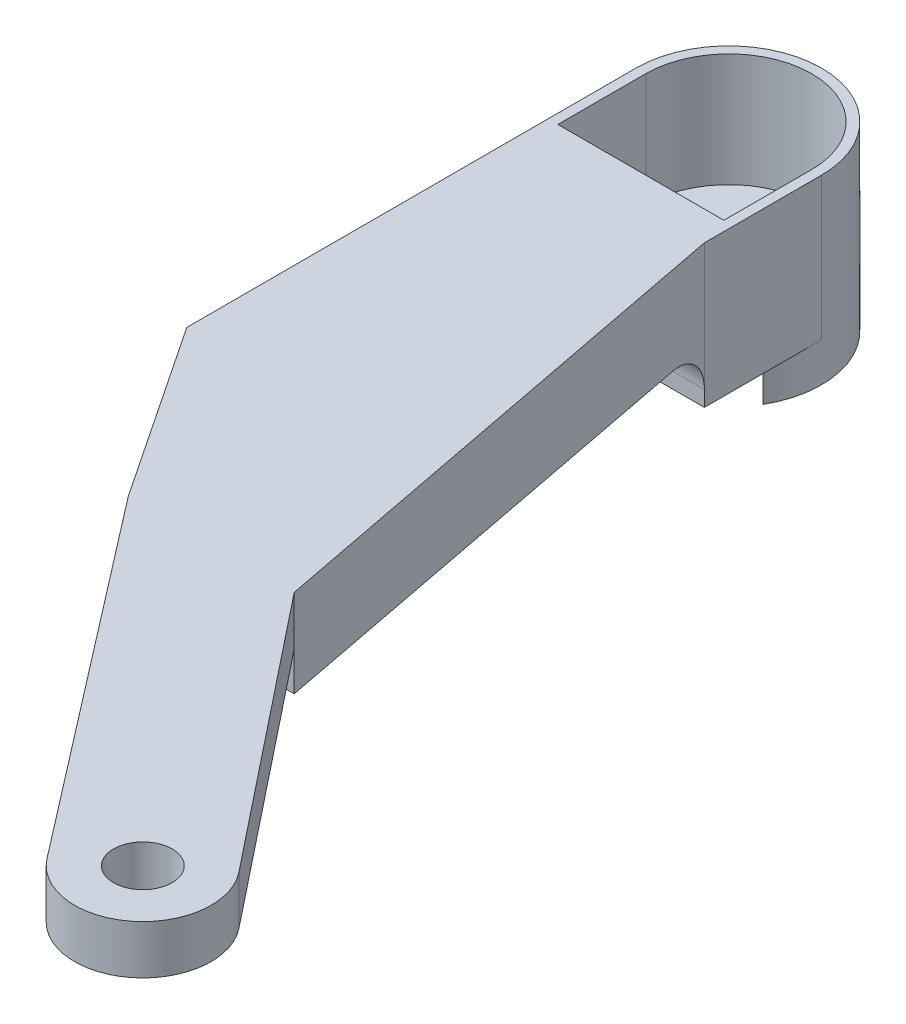
SolidWorks part; units mm, degrees
ref_plane "Front Plane" through (0, 0, 0) normal (0, 0, 1) x (1, 0, 0)
ref_plane "Top Plane" through (0, 0, 0) normal (0, 1, 0) x (1, 0, 0)
ref_plane "Right Plane" through (0, 0, 0) normal (1, 0, 0) x (0, 0, -1)
sketch "Sketch1" plane through (0, 0, 0) normal (0, 1, 0) x (1, 0, 0)
  line L0 (-2.75, 0) -> (-5.5779, -4.898)
  line L1 (2.75, 0) -> (5.5779, -4.898)
  line L2 (5.5779, -4.898) -> (-5.5779, -4.898) construction
  line L4 (0, -4.898) -> (0, 0) construction
  circle A0 centre (0, 0) radius 2.75
  circle A1 centre (0, 0) radius 4.75
  dimension "D1" = 5.5
  dimension "D2" = 2
  dimension "D3" = 60
extrude "Boss-Extrude1" add sketch "Sketch1" along normal blind 2 contours L1 A1 L0 A0 region at (-3.5365, 0, 1.1249)
sketch "Sketch2" plane through (0, 2, 0) normal (0, 1, 0) x (1, 0, 0)
  arc A0 (4.1174, -2.3684) -> (-4.1174, -2.3684) centre (0, 0) ccw construction
  circle A1 centre (0, 0) radius 4.75
  circle A2 centre (0, 0) radius 1.4
  dimension "D1" = 2.8
extrude "Boss-Extrude2" add sketch "Sketch2" along normal blind 1.5
sketch "Sketch3" plane through (0, 3.5, 0) normal (0, 1, 0) x (1, 0, 0)
  line L0 (-4.75, 0) -> (-4.75, -6)
  line L1 (-4.75, -6) -> (4.75, -6)
  line L2 (4.75, -6) -> (4.75, 0)
  line L3 (-4.75, 0) -> (4.75, 0) construction
  circle A0 centre (0, 0) radius 4.5
  circle A1 centre (0, 0) radius 4.75 construction
  circle A2 centre (0, 0) radius 4.75
  point P10 (-4.748, -0.1383)
  point P11 (-4.75, -0.1031)
  circle M5 centre (0, 0) radius 4.75
  dimension "D1" = 9
  dimension "D2" = 1.5
extrude "Boss-Extrude3" add sketch "Sketch3" against normal blind 1.5 contours L1 L2 L0 M5 region at (0, 3.5, 4.8624)
sketch "Sketch4" plane through (0, 3.5, 0) normal (0, 1, 0) x (1, 0, 0)
  line L0 (4.75, -6) -> (4.75, 0) construction
  line L1 (-4.75, -6) -> (4.75, -6)
  line L2 (-4.75, -6) -> (-4.75, -4.5)
  line L3 (-4.75, -4.5) -> (4.75, -4.5)
  line L4 (4.75, -6) -> (4.75, -4.5)
  dimension "D1" = 1.5
extrude "Boss-Extrude4" add sketch "Sketch4" along normal offset from surface (2.3 mm away) 3.8 up to face at (0, 2, 1.7587)
sketch "Sketch5" plane through (0, 5.8, 0) normal (0, 1, 0) x (1, 0, 0)
  line L0 (-4.75, -4.5) -> (-4.75, -23)
  line L1 (-4.75, -23) -> (1.25, -32)
  line L2 (1.25, -32) -> (9.75, -32)
  line L3 (9.75, -32) -> (4.75, -6)
  line L4 (4.75, -6) -> (4.75, -4.5)
  line L5 (4.75, -4.5) -> (-4.75, -4.5)
  dimension "D1" = 32
  dimension "D2" = 9
  dimension "D3" = 6
  dimension "D4" = 5
extrude "Boss-Extrude5" add sketch "Sketch5" along normal blind 1
sketch "Sketch6" plane through (0, 6.8, 0) normal (0, 1, 0) x (1, 0, 0)
  line L0 (9.75, -32) -> (20.7396, -45.8218)
  line L1 (1.25, -32) -> (15.2278, -50.1365)
  line L2 (1.25, -32) -> (9.75, -32) construction
  line L3 (1.25, -32) -> (9.75, -32)
  line L10 (4.75, -4.5) -> (-4.75, -4.5)
  line L11 (-4.75, -4.5) -> (-4.75, -23)
  line L12 (-4.75, -23) -> (1.25, -32)
  line L13 (1.25, -32) -> (9.75, -32)
  line L14 (9.75, -32) -> (4.75, -6)
  line L15 (4.75, -6) -> (4.75, -4.5)
  line L16 (4.75, -4.5) -> (-4.75, -4.5)
  line L17 (-4.75, -4.5) -> (-4.75, -23)
  line L18 (-4.75, -23) -> (1.25, -32)
  line L19 (1.25, -32) -> (9.75, -32)
  line L20 (9.75, -32) -> (4.75, -6)
  line L21 (4.75, -6) -> (4.75, -4.5)
  circle A0 centre (18, -48) radius 1.5
  circle A1 centre (18, -48) radius 3.5
  line M9 (4.75, -4.5) -> (-4.75, -4.5)
  line M10 (-4.75, -4.5) -> (-4.75, -23)
  line M11 (-4.75, -23) -> (1.25, -32)
  line M12 (1.25, -32) -> (9.75, -32)
  line M13 (9.75, -32) -> (4.75, -6)
  line M14 (4.75, -6) -> (4.75, -4.5)
  dimension "D3" = 3
  dimension "D1" = 18
  dimension "D2" = 48
  dimension "D4" = 2
  dimension "D5" = 0
extrude "Boss-Extrude6" add sketch "Sketch6" along normal blind 1.5 contours M14 M9 M10 M11 M12 M13 | A1 L0 L1 M12 | A1 A0 region at (10.768, 6.8, 39.0264) region at (1.6419, 6.8, 18.3842) region at (21.211, 6.8, 46.8791)
sketch "Sketch7" plane through (0, 3.5, 0) normal (0, 1, 0) x (1, 0, 0)
  line L0 (-4.75, 0) -> (-4.75, -4.5)
  line L1 (-4.75, -4.5) -> (-4.25, -4.5)
  line L2 (-4.25, -4.5) -> (-4.25, 0)
  line L3 (4.25, 0) -> (4.25, -4.5)
  line L4 (4.75, -4.5) -> (-4.75, -4.5) construction
  line L5 (4.25, -4.5) -> (4.75, -4.5)
  line L6 (4.75, -4.5) -> (4.75, 0)
  arc A0 (4.75, 0) -> (-4.75, 0) centre (0, 0) ccw construction
  arc A1 (4.75, 0) -> (-4.75, 0) centre (0, 0) ccw
  arc A2 (4.25, 0) -> (-4.25, 0) centre (0, 0) ccw
  dimension "D1" = 0.5
extrude "Boss-Extrude7" add sketch "Sketch7" along normal up to vertex (4.8 mm away) up to point (4.75, 8.3, 4.5)
sketch "Sketch8" plane through (0, 5.8, 0) normal (0, -1, 0) x (1, 0, 0)
  line L5 (-4.75, 23) -> (-4.75, 6)
  line L6 (-4.75, 6) -> (4.75, 6)
  line L7 (4.75, 6) -> (9.75, 32)
  line L8 (9.75, 32) -> (1.25, 32)
  line L9 (1.25, 32) -> (-4.75, 23)
  line L10 (-4.75, 23) -> (-4.75, 6)
  line L11 (-4.75, 6) -> (4.75, 6)
  line L12 (4.75, 6) -> (9.75, 32)
  line L13 (9.75, 32) -> (1.25, 32)
  line L14 (1.25, 32) -> (-4.75, 23)
  dimension "D1" = 0
extrude "Boss-Extrude8" add sketch "Sketch8" along normal blind 1
fillet "Fillet1" radius 2 1 edges at (0, 4.8, 6)
sketch "Sketch9" plane through (0, 8.3, 0) normal (0, 1, 0) x (1, 0, 0)
  line L3 (-4.25, -4.5) -> (4.25, -4.5)
  line L4 (-4.25, 0) -> (-4.25, -4.5)
  line L5 (4.25, -4.5) -> (4.25, 0)
  line L6 (4.75, -6) -> (4.75, 0)
  line L7 (-4.75, 0) -> (-4.75, -23)
  line L8 (-4.75, -23) -> (1.25, -32)
  line L9 (1.25, -32) -> (15.2278, -50.1365)
  line L10 (20.7396, -45.8218) -> (9.75, -32)
  line L11 (9.75, -32) -> (4.75, -6)
  line L12 (4.75, -6) -> (4.75, 0)
  line L13 (-4.75, 0) -> (-4.75, -23)
  line L14 (-4.75, -23) -> (1.25, -32)
  line L15 (1.25, -32) -> (15.2278, -50.1365)
  line L16 (20.7396, -45.8218) -> (9.75, -32)
  line L17 (9.75, -32) -> (4.75, -6)
  line L18 (-4.25, -4.5) -> (4.25, -4.5)
  line L19 (-4.25, 0) -> (-4.25, -4.5)
  line L20 (4.25, -4.5) -> (4.25, 0)
  circle A0 centre (18, -48) radius 1.5 construction
  circle A1 centre (18, -48) radius 1.5
  arc A2 (4.75, 0) -> (-4.75, 0) centre (0, 0) ccw
  arc A3 (15.2278, -50.1365) -> (20.7396, -45.8218) centre (18, -48) ccw
  arc A4 (4.75, 0) -> (-4.75, 0) centre (0, 0) ccw
  arc A5 (15.2278, -50.1365) -> (20.7396, -45.8218) centre (18, -48) ccw
  arc A7 (4.25, 0) -> (-4.25, 0) centre (0, 0) ccw
  arc A8 (4.25, 0) -> (-4.25, 0) centre (0, 0) ccw
  dimension "D1" = 0
  dimension "D2" = 0
extrude "Boss-Extrude9" add sketch "Sketch9" along normal blind 1
sketch "Sketch10" plane through (0, 3.5, 0) normal (0, 1, 0) x (1, 0, 0)
  circle A0 centre (0, 0) radius 1.4 construction
  circle A1 centre (0, 0) radius 1.4
extrude "Boss-Extrude10" add sketch "Sketch10" against normal blind 0.2
